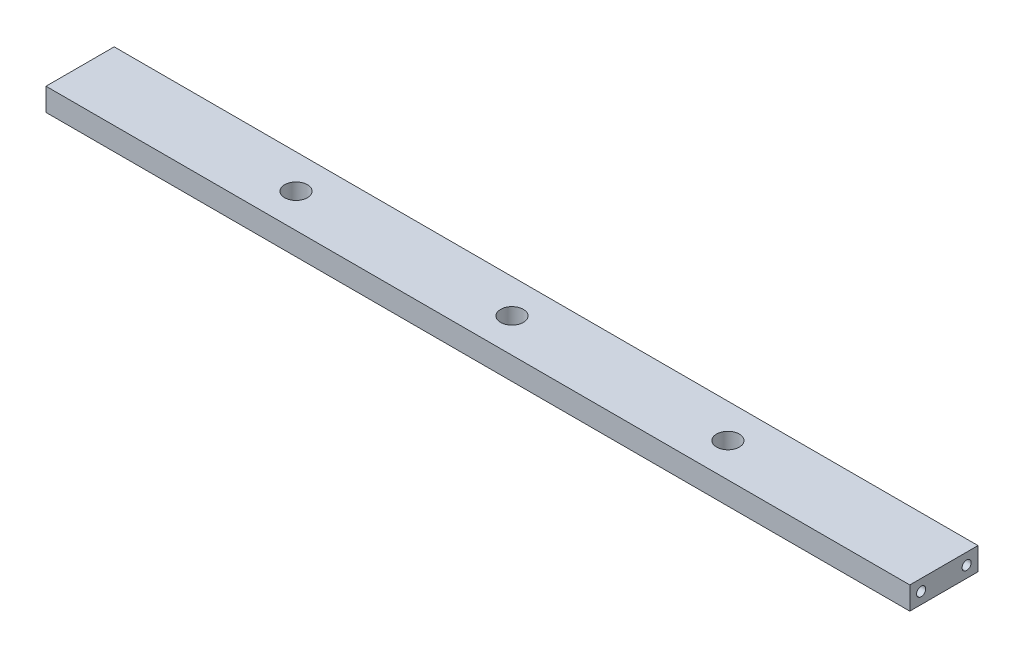
SolidWorks part; units mm, degrees
material "6061 Alloy"
ref_plane "Front Plane" through (0, 0, 0) normal (0, 0, 1) x (1, 0, 0)
ref_plane "Top Plane" through (0, 0, 0) normal (0, 1, 0) x (1, 0, 0)
ref_plane "Right Plane" through (0, 0, 0) normal (1, 0, 0) x (0, 0, -1)
sketch "Sketch1" plane through (0, 0, 0) normal (1, 0, 0) x (0, 0, -1)
  line L1 (-19.05, -6.35) -> (19.05, -6.35)
  line L2 (-19.05, -6.35) -> (-19.05, 6.35)
  line L3 (-19.05, 6.35) -> (19.05, 6.35)
  line L4 (19.05, -6.35) -> (19.05, 6.35)
  line L5 (-19.05, -6.35) -> (19.05, 6.35) construction
  line L6 (-19.05, 6.35) -> (19.05, -6.35) construction
  point P0 (0, 0)
  dimension "D1" = 38.1
  dimension "D2" = 12.7
extrude "Boss-Extrude1" add sketch "Sketch1" along normal mid plane 482.6
hole_wizard "1/4-20 Tapped Hole1" positions "3DSketch1" profile "Sketch3" tap size "1/4-20" standard "ANSI Inch"
sketch3d "3DSketch1"
  line L4 (241.3, 0, 19.05) -> (241.3, 0, 12.7) construction
  line L5 (241.3, 6.35, 19.05) -> (241.3, -6.35, 19.05) construction
  line L6 (241.3, 0, 12.7) -> (241.3, 0, -12.7) construction
  line L7 (241.3, 0, -12.7) -> (241.3, 0, -19.05) construction
  line L8 (241.3, -6.35, -19.05) -> (241.3, 6.35, -19.05) construction
  point P0 (241.3, 0, 12.7)
  point P2 (241.3, 0, -12.7)
  dimension "D1" = 25.4
sketch "Sketch3" plane through (241.3, 0, 12.7) normal (0, 1, 0) x (0, 0, -1)
  line L0 (0, 0) -> (0, 20.5838)
  line L1 (0, 20.5838) -> (2.5527, 19.05)
  line L2 (2.5527, 19.05) -> (2.5527, 0)
  line L5 (2.5527, 0) -> (0, 0)
  line L10 (0, 20.5838) -> (-2.5527, 19.05) construction
  line L11 (0, -6.35) -> (0, 107.95) construction
  dimension "Tap Drill Dia." = 5.1054
  dimension "Tap Drill Depth" = 19.05
  dimension "Drill Angle" = 118
sketch "Sketch2" plane through (0, 6.35, 0) normal (0, 1, 0) x (1, 0, 0)
  line L0 (0, 0) -> (241.3, 0) construction
  line L1 (241.3, -19.05) -> (241.3, 19.05) construction
  circle A0 centre (0, 0) radius 6.35
  circle A1 centre (120.65, 0) radius 6.35
  dimension "D1" = 12.7
extrude "Cut-Extrude1" cut sketch "Sketch2" against normal through all
sketch "Sketch4" plane through (0, -6.35, 0) normal (0, -1, 0) x (1, 0, 0)
  line L1 (12.7, 12.7) -> (107.95, 12.7)
  line L2 (133.35, 12.7) -> (212.725, 12.7)
  line L3 (215.9, 9.525) -> (215.9, -9.525)
  line L4 (212.725, -12.7) -> (133.35, -12.7)
  line L5 (107.95, -12.7) -> (12.7, -12.7)
  line L6 (241.3, 0) -> (215.9, 0) construction
  line L8 (241.3, 19.05) -> (241.3, -19.05) construction
  line L9 (241.3, 19.05) -> (-241.3, 19.05) construction
  arc A0 (10.16, -7.62) -> (10.16, 7.62) centre (0, 0) ccw
  arc A1 (110.49, 7.62) -> (110.49, -7.62) centre (120.65, 0) ccw
  arc A2 (130.81, 7.62) -> (130.81, -7.62) centre (120.65, 0) cw
  arc A3 (130.81, 7.62) -> (133.35, 12.7) centre (133.35, 9.525) cw
  arc A4 (130.81, -7.62) -> (133.35, -12.7) centre (133.35, -9.525) ccw
  arc A5 (110.49, -7.62) -> (107.95, -12.7) centre (107.95, -9.525) cw
  arc A6 (215.9, -9.525) -> (212.725, -12.7) centre (212.725, -9.525) cw
  arc A7 (212.725, 12.7) -> (215.9, 9.525) centre (212.725, 9.525) cw
  arc A8 (10.16, -7.62) -> (12.7, -12.7) centre (12.7, -9.525) ccw
  arc A9 (10.16, 7.62) -> (12.7, 12.7) centre (12.7, 9.525) cw
  arc A10 (110.49, 7.62) -> (107.95, 12.7) centre (107.95, 9.525) ccw
  dimension "D3" = 25.4
  dimension "D4" = 3.175
  dimension "D1" = 12.7
  dimension "D2" = 6.35
extrude "Cut-Extrude2" cut sketch "Sketch4" against normal blind 9.525
mirror "Mirror2" about plane through (0, 0, 0) normal (1, 0, 0) of "Cut-Extrude2", "Cut-Extrude1", "1/4-20 Tapped Hole1"
